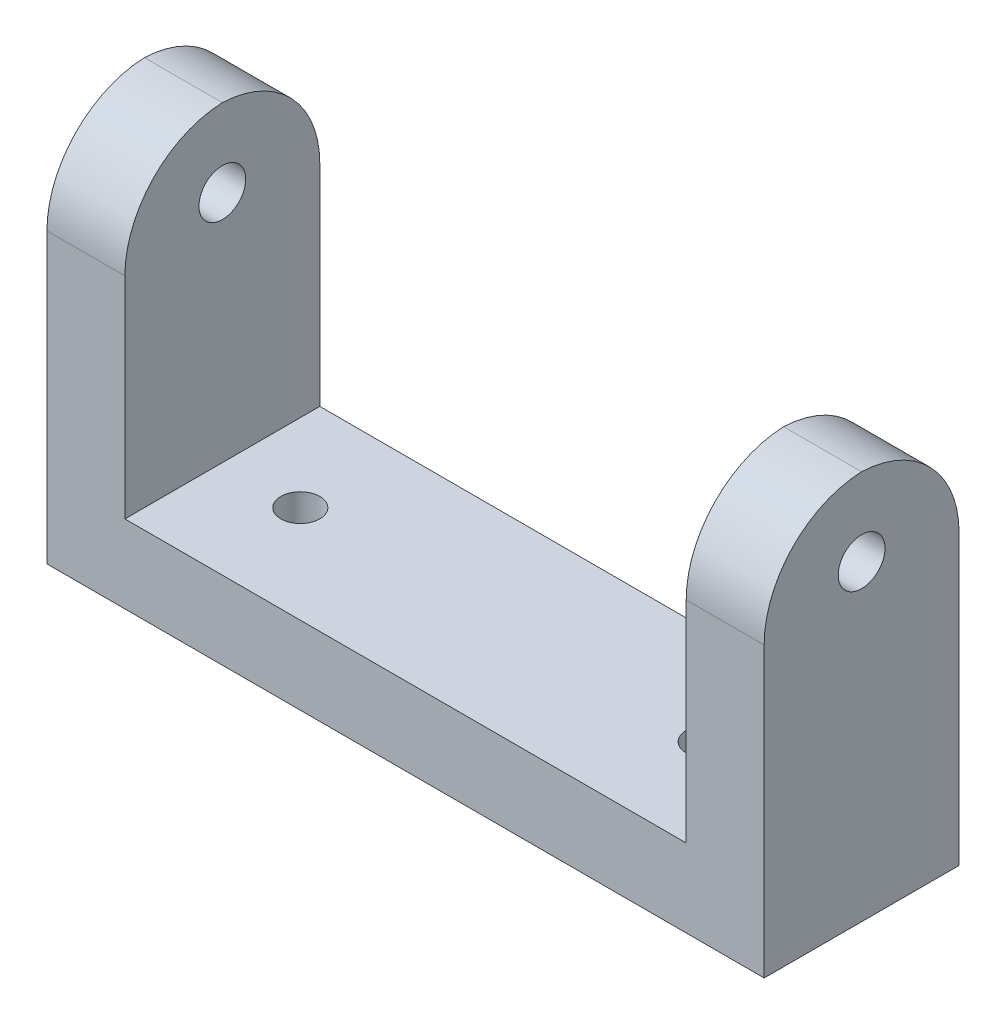
SolidWorks part; units mm, degrees
ref_plane "Front" through (0, 0, 0) normal (0, 0, 1) x (1, 0, 0)
ref_plane "Top" through (0, 0, 0) normal (0, 1, 0) x (1, 0, 0)
ref_plane "Right" through (0, 0, 0) normal (1, 0, 0) x (0, 0, -1)
sketch "Sketch1" plane through (0, 0, 0) normal (0, 0, 1) x (1, 0, 0)
  line L0 (0, 50) -> (10, 50)
  line L1 (10, 50) -> (10, 10)
  line L2 (10, 10) -> (82, 10)
  line L3 (82, 10) -> (82, 50)
  line L4 (82, 50) -> (92, 50)
  line L5 (92, 50) -> (92, 0)
  line L6 (92, 0) -> (0, 0)
  line L7 (0, 0) -> (0, 50)
  dimension "D1" = 72
  dimension "D2" = 10
  dimension "D3" = 10
  dimension "D4" = 10
  dimension "D5" = 50
extrude "Boss-Extrude1" add sketch "Sketch1" along normal blind 25
sketch "Sketch2" plane through (92, 0, 0) normal (1, 0, 0) x (0, 0, -1)
  line L0 (-25, 50) -> (0, 50) construction
  line L1 (0, 0) -> (0, 50) construction
  circle A0 centre (-12.5, 40) radius 3
  dimension "D1" = 6
  dimension "D2" = 10
  dimension "D3" = 12.5
extrude "Cut-Extrude1" cut sketch "Sketch2" against normal through all
sketch "Sketch3" plane through (0, 10, 0) normal (0, 1, 0) x (1, 0, 0)
  line L0 (10, -25) -> (10, 0) construction
  line L1 (82, -25) -> (82, 0) construction
  line L2 (82, 0) -> (10, 0) construction
  circle A0 centre (20, -12.5) radius 2.5
  circle A1 centre (72, -12.5) radius 2.5
  dimension "D1" = 5
  dimension "D2" = 5
  dimension "D3" = 10
  dimension "D4" = 10
  dimension "D5" = 12.5
extrude "Cut-Extrude2" cut sketch "Sketch3" against normal blind 20
fillet "Fillet2" radius 13 4 edges at (87, 50, 0) (87, 50, 25) (5, 50, 25) (5, 50, 0)
